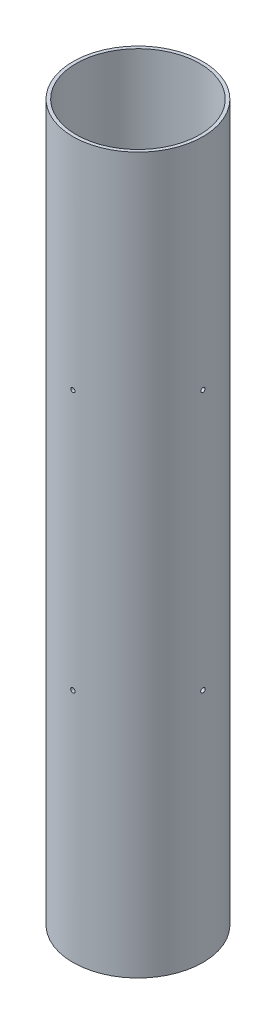
SolidWorks part; units mm, degrees
material "E-Glass Fiber"
ref_plane "Front Plane" through (0, 0, 0) normal (0, 0, 1) x (1, 0, 0)
ref_plane "Top Plane" through (0, 0, 0) normal (0, 1, 0) x (1, 0, 0)
ref_plane "Right Plane" through (0, 0, 0) normal (1, 0, 0) x (0, 0, -1)
sketch "Sketch1" plane through (0, 0, 0) normal (0, 1, 0) x (1, 0, 0)
  circle A0 centre (0, 0) radius 50.8
  dimension "D1" = 101.6
extrude "Coupler Extrusion" add sketch "Sketch1" along normal blind 558.8 thin thin type one direction reverse wall 2.54
ref_plane "Plane1" through (0, 0, 50.8) normal (0, 0, 1) x (1, 0, 0)
sketch "Sketch2" plane through (0, 0, 50.8) normal (0, 0, 1) x (1, 0, 0)
  line L0 (0, 558.8) -> (0, 0) construction
  line L1 (48.26, 558.8) -> (-48.26, 558.8) construction
  circle A0 centre (0, 387.35) radius 1.6383
  dimension "D1" = 3.2766
  dimension "D2" = 171.45
extrude "Bulkhead Hole" cut sketch "Sketch2" against normal up to next
pattern_circular "CirPattern1" count 4 over 360 about axis through (0, 558.8, 0) along (0, -1, 0) of "Bulkhead Hole"
sketch "Sketch3" plane through (0, 0, 50.8) normal (0, 0, 1) x (1, 0, 0)
  line L0 (0, 558.8) -> (0, 0) construction
  line L1 (50.8, 558.8) -> (-50.8, 558.8) construction
  line L2 (-48.26, 0) -> (48.26, 0) construction
  line L3 (-50.8, 0) -> (50.8, 0) construction
  line L4 (48.26, 558.8) -> (-48.26, 558.8) construction
  circle A0 centre (0, 184.15) radius 1.7526
  dimension "D1" = 3.5052
  dimension "D2" = 184.15
  dimension "D3" = 374.65
extrude "Lower Bulkhead Hole" cut sketch "Sketch3" against normal up to next
pattern_circular "CirPattern2" count 4 over 360 about axis through (0, 558.8, 0) along (0, -1, 0) of "Lower Bulkhead Hole" reverse direction yes
